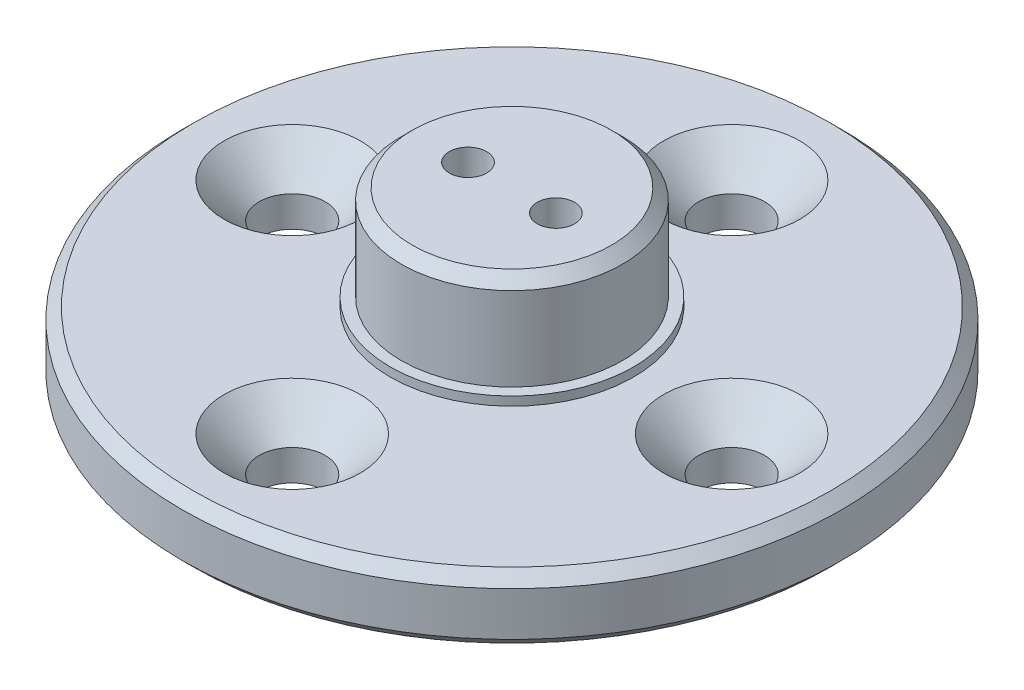
SolidWorks part; units mm, degrees
ref_plane "前视基准面" through (0, 0, 0) normal (0, 0, 1) x (1, 0, 0)
ref_plane "上视基准面" through (0, 0, 0) normal (0, 1, 0) x (1, 0, 0)
ref_plane "右视基准面" through (0, 0, 0) normal (1, 0, 0) x (0, 0, -1)
other "Configuration Table"
sketch "草图1" plane through (0, 0, 0) normal (0, 1, 0) x (1, 0, 0)
  line L0 (-21.98, 0) -> (22.6908, 0) construction
  line L1 (0, 22.7485) -> (0, -21.9381) construction
  circle A0 centre (0, 0) radius 15
  circle A1 centre (0, 10) radius 1.5
  circle A2 centre (10, 0) radius 1.5
  circle A3 centre (0, -10) radius 1.5
  circle A4 centre (-10, 0) radius 1.5
  point P15 (0, 0)
  dimension "D1" = 3
  dimension "D3" = 30
  dimension "D2" = 10
extrude "凸台-拉伸1" add sketch "草图1" along normal blind 3
sketch "草图2" plane through (0, 3, 0) normal (0, 1, 0) x (1, 0, 0)
  line L0 (0, 1.9211) -> (0, -1.7964) construction
  line L1 (-1.959, 0) -> (1.7076, 0) construction
  circle A1 centre (0, 0) radius 5.035
  circle A3 centre (2, 0) radius 0.85
  circle A4 centre (-2, 0) radius 0.85
  dimension "D1" = 10.07
  dimension "D2" = 1.7
  dimension "D3" = 4
extrude "凸台-拉伸2" add sketch "草图2" along normal blind 4.7
sketch "草图4" plane through (0, 3, 0) normal (0, 1, 0) x (1, 0, 0)
  circle A8 centre (0, 0) radius 5.535
  circle A9 centre (0, 0) radius 5.035 construction
  point P15 (0, 0)
  dimension "D1" = 0.5
extrude "凸台-拉伸3" add sketch "草图4" along normal blind 0.4
chamfer "倒角1" distance 0.5 angle 45 1 edges at (0, 7.7, 5.035)
chamfer "倒角3" distance 0.5 angle 45 2 edges at (0, 0, 15) (0, 3, 15)
chamfer "倒角4" distance 1.6 angle 45 4 edges at (10, 3, 1.5) (0, 3, 11.5) (-10, 3, 1.5) (0, 3, -8.5)
sketch "草图5" plane through (0, 7.7, 0) normal (0, 1, 0) x (1, 0, 0)
  circle A0 centre (2, 0) radius 0.85 construction
  circle A1 centre (-2, 0) radius 0.85 construction
  circle A2 centre (2, 0) radius 0.85
  circle A3 centre (-2, 0) radius 0.85
extrude "切除-拉伸1" cut sketch "草图5" against normal blind 10
